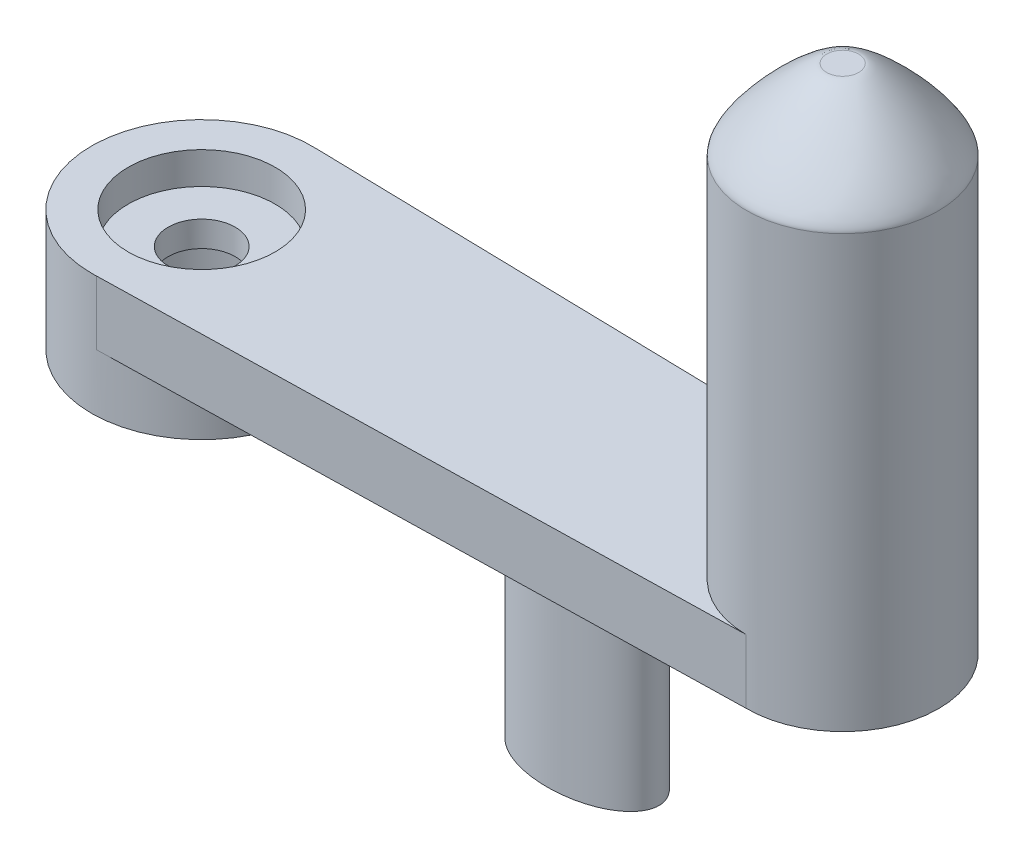
SolidWorks part; units mm, degrees
material "PVC Rígido"
ref_plane "Plano frontal" through (0, 0, 0) normal (0, 0, 1) x (1, 0, 0)
ref_plane "Plano superior" through (0, 0, 0) normal (0, 1, 0) x (1, 0, 0)
ref_plane "Plano direito" through (0, 0, 0) normal (1, 0, 0) x (0, 0, -1)
sketch "Esboço1" plane through (0, 0, 0) normal (0, 1, 0) x (1, 0, 0)
  line L0 (0, 0) -> (-14.05, 0) construction
  circle A0 centre (0, 0) radius 3.45
  dimension "D1" = 6.9
extrude "Ressalto-extrusão1" add sketch "Esboço1" against normal blind 1.4
sketch "Esboço2" plane through (0, -1.4, 0) normal (0, -1, 0) x (1, 0, 0)
  circle A1 centre (0, 0) radius 3.45
  circle A2 centre (0, 0) radius 3.45 construction
extrude "Ressalto-extrusão2" add sketch "Esboço2" along normal offset from surface (2.4 mm away) 3.8 up to face at (0, 0, 3.45)
hole_wizard "Furo1" positions "Esboço3" profile "Esboço4" legacy
sketch "Esboço3" plane through (0, -3.8, 0) normal (0, -1, 0) x (-1, 0, 0)
  point P0 (0, 0)
sketch "Esboço4" plane through (0, -3.8, 0) normal (1, 0, 0) x (0, 0, -1)
  line L0 (0, 0) -> (0, 2)
  line L1 (0, 2) -> (2.475, 2)
  line L2 (2.475, 2) -> (2.475, 0)
  line L3 (2.475, 0) -> (0, 0)
  line L4 (0, 110) -> (0, -10) construction
  dimension "Diameter" = 4.95
  dimension "Depth" = 2
hole_wizard "Furo2" positions "Esboço5" profile "Esboço6" legacy
sketch "Esboço5" plane through (0, 0, 0) normal (0, 1, 0) x (1, 0, 0)
  point P0 (0, 0)
sketch "Esboço6" plane through (0, 0, 0) normal (1, 0, 0) x (0, 0, 1)
  line L0 (0, 0) -> (0, 1)
  line L1 (0, 1) -> (2.3, 1)
  line L2 (2.3, 1) -> (2.3, 0)
  line L3 (2.3, 0) -> (0, 0)
  line L4 (0, 110) -> (0, -10) construction
  dimension "Diameter" = 4.6
  dimension "Depth" = 1
hole_wizard "Furo3" positions "Esboço7" profile "Esboço8" legacy end condition through all
sketch "Esboço7" plane through (0, 0, 0) normal (0, 1, 0) x (1, 0, 0)
  point P0 (0, 0)
sketch "Esboço8" plane through (0, 0, 0) normal (1, 0, 0) x (0, 0, 1)
  line L0 (0, 0) -> (0, 3.8)
  line L1 (0, 3.8) -> (1.05, 3.8)
  line L2 (1.05, 3.8) -> (1.05, 0)
  line L3 (1.05, 0) -> (0, 0)
  line L4 (0, 110) -> (0, -10) construction
  dimension "Diameter" = 2.1
  dimension "Depth" = 3.8
sketch "Sketch2" plane through (0, 0, 0) normal (0, 1, 0) x (1, 0, 0)
  line L0 (0, 0) -> (20, 0) construction
  line L1 (0, 3.45) -> (20.0674, 2.9992)
  line L2 (0, -3.45) -> (20.0674, -2.9992)
  line L3 (0, 4.7476) -> (0, -3.6033) construction
  circle A0 centre (0, 0) radius 3.45 construction
  arc A1 (20.0674, 2.9992) -> (20.0674, -2.9992) centre (20, 0) cw
  circle A4 centre (0, 0) radius 3.45
  arc A5 (0, -3.45) -> (0, 3.45) centre (0, 0) ccw
  circle M3 centre (0, 0) radius 3.45
  dimension "D2" = 3
  dimension "D1" = 20
  dimension "D3" = 0
extrude "Boss-Extrude1" add sketch "Sketch2" against normal blind 2 contours A1 L1 L2 M3 region at (12.3222, 0, 0)
sketch "Sketch3" plane through (0, -2, 0) normal (0, -1, 0) x (1, 0, 0)
  line L0 (20.0674, 2.9992) -> (20.0674, -2.9992) construction
  circle A0 centre (20.0674, 0) radius 3
  dimension "D1" = 6
extrude "Boss-Extrude2" add sketch "Sketch3" against normal blind 16 contours A0
sketch "Esboço11" [suppressed] plane through (0, -3.8, 0) normal (0, -1, 0) x (1, 0, 0)
  line L0 (-0.0981, 2.4731) -> (0, 2.375)
  line L1 (0, 2.375) -> (0.0981, 2.4731)
  line L2 (0, 0) -> (0, 2.475) construction
  circle A0 centre (0, 0) radius 2.375 construction
  circle A1 centre (0, 0) radius 2.475
  arc A2 (0.0981, 2.4731) -> (-0.0981, 2.4731) centre (0, 0) ccw
  dimension "D3" = 4.75
  dimension "D2" = 0.1
  dimension "D1" = 0
extrude "Ressalto-extrusão3" [suppressed] add sketch "Esboço11" against normal up to surface (2 mm away)
sketch "Sketch1" [suppressed] plane through (0, 0, 0) normal (1, 0, 0) x (0, 0, -1)
  line L0 (0, 0) -> (0, -4.3951) construction
pattern_circular "PadrãoCircular1" [suppressed] count 60 over 360 of bodies 117
sketch "Sketch4" plane through (0, -2, 0) normal (0, -1, 0) x (1, 0, 0)
  line L0 (0, 0) -> (23.0674, 0) construction
  arc A0 (20.0395, -2.9999) -> (20.0395, 2.9999) centre (20.0674, 0) ccw construction
  ellipse E0 centre (12.0674, 0) end of major axis (14.3174, 0) minor radius 1.25
  dimension "D1" = 2.25
  dimension "D2" = 2.5
  dimension "D3" = 11
extrude "Boss-Extrude3" add sketch "Sketch4" along normal blind 7
fillet "Fillet3" radius 2.5 1 edges at (20.0674, 14, -3) conic rho 0.15
